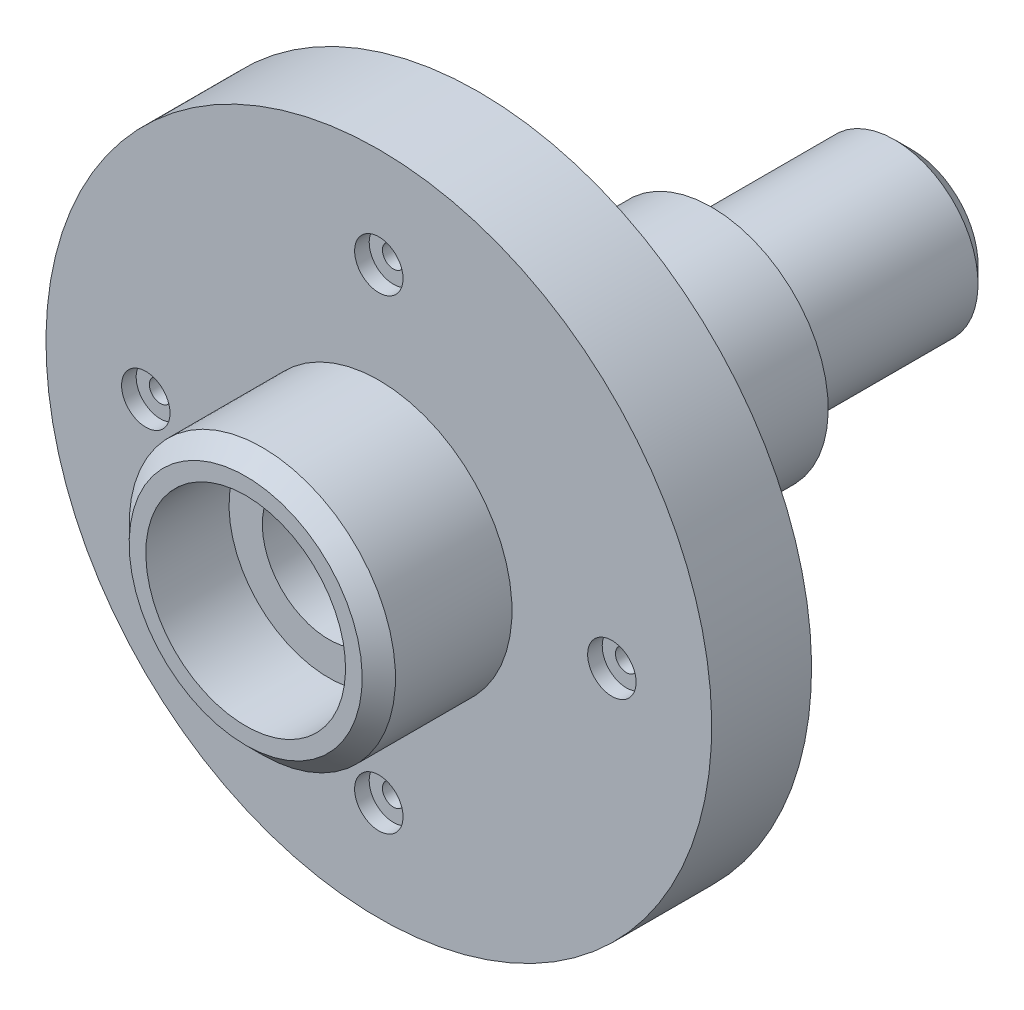
SolidWorks part; units mm, degrees
ref_plane "Front Plane" through (0, 0, 0) normal (0, 0, 1) x (1, 0, 0)
ref_plane "Top Plane" through (0, 0, 0) normal (0, 1, 0) x (1, 0, 0)
ref_plane "Right Plane" through (0, 0, 0) normal (1, 0, 0) x (0, 0, -1)
sketch "Sketch1" plane through (0, 0, 0) normal (1, 0, 0) x (0, 0, -1)
  line L0 (0, 0) -> (-155, 0) construction
  line L1 (-200, 30) -> (-200, 40)
  line L2 (-200, 40) -> (-160, 40)
  line L3 (-160, 40) -> (-160, 100)
  line L4 (-160, 100) -> (-130, 100)
  line L5 (-130, 100) -> (-130, 35)
  line L6 (-130, 35) -> (-60, 35)
  line L7 (-60, 35) -> (-60, 25)
  line L8 (-60, 25) -> (0, 25)
  line L9 (0, 25) -> (0, 0)
  line L10 (0, 0) -> (-155, 0)
  line L11 (-200, 30) -> (-175, 30)
  line L12 (-175, 30) -> (-175, 20)
  line L13 (-175, 20) -> (-155, 20)
  line L14 (-155, 20) -> (-155, 0)
  point P16 (-172.3026, 0)
  dimension "D1" = 200
  dimension "D2" = 200
  dimension "D3" = 30
  dimension "D4" = 60
  dimension "D5" = 70
  dimension "D6" = 40
  dimension "D7" = 80
  dimension "D8" = 70
  dimension "D9" = 50
  dimension "D10" = 20
  dimension "D11" = 30
  dimension "D12" = 20
  dimension "D13" = 25
revolve "Revolve1" add sketch "Sketch1" angle 360 about L0
sketch "Sketch2" plane through (0, 0, 0) normal (1, 0, 0) x (0, 0, -1)
  line L0 (-130, -35) -> (-60, -35) construction
  line L1 (-130, -100) -> (-130, 100) construction
  circle A0 centre (-90, -50) radius 30
  dimension "D2" = 60
  dimension "D1" = 15
  dimension "D3" = 40
extrude "Cut-Extrude1" cut sketch "Sketch2" against normal blind 10 and the other way blind 10
sketch "Sketch5" plane through (0, 0, 160) normal (0, 0, 1) x (1, 0, 0)
  line L0 (0, 0) -> (100, 0) construction
  circle A0 centre (0, 0) radius 100 construction
  point P5 (70, 0)
  point P6 (0, 0)
  point P9 (0, -70)
  point P10 (-70, 0)
  point P11 (0, 70)
  dimension "D2" = 4
hole_wizard "CBORE for M6 Hex Head Bolt2" positions "3DSketch3" profile "Sketch6" counterbore size "M6" standard "ANSI Metric" end condition through all
sketch3d "3DSketch3"
  point P0 (0, 70, 160)
  point P3 (70, 0, 160)
  point P6 (0, -70, 160)
  point P9 (-70, 0, 160)
sketch "Sketch6" plane through (0, 70, 160) normal (1, 0, 0) x (0, -1, 0)
  line L0 (0, 0) -> (0, 160)
  line L1 (0, 160) -> (3.3, 160)
  line L3 (3.3, 160) -> (3.3, 4.38)
  line L4 (3.3, 4.38) -> (7.275, 4.38)
  line L5 (7.275, 4.38) -> (7.275, 0)
  line L7 (7.275, 0) -> (0, 0)
  line L11 (0, -6.35) -> (0, 107.95) construction
  dimension "Thru Hole Dia." = 6.6
  dimension "Thru Hole Depth" = 160
  dimension "C'Bore Dia." = 14.55
  dimension "C'Bore Depth" = 4.38
chamfer "Chamfer1" distance 5 angle 45 2 edges at (0, 25, 0) (0, 40, 200)
hole_wizard "M20x1.5 Tapped Hole1" positions "3DSketch6" profile "Sketch9" tap size "M20x1.5" standard "ANSI Metric"
sketch3d "3DSketch6"
  point P0 (0, 0, 0)
  point P4 (0, 0, 0)
  point P7 (0, 0, 0)
sketch "Sketch9" plane through (0, 0, 0) normal (1, 0, 0) x (0, 1, 0)
  line L0 (0, 0) -> (0, 55.558)
  line L1 (0, 55.558) -> (9.25, 50)
  line L2 (9.25, 50) -> (9.25, 0)
  line L5 (9.25, 0) -> (0, 0)
  line L10 (0, 55.558) -> (-9.25, 50) construction
  line L11 (0, -6.35) -> (0, 107.95) construction
  dimension "Tap Drill Dia." = 18.5
  dimension "Tap Drill Depth" = 50
  dimension "Drill Angle" = 118
cosmetic thread "Hole Thread5" parameters "D1"=45, "D2"=20
cosmetic thread "Hole Thread6" parameters "D1"=45, "D2"=20
